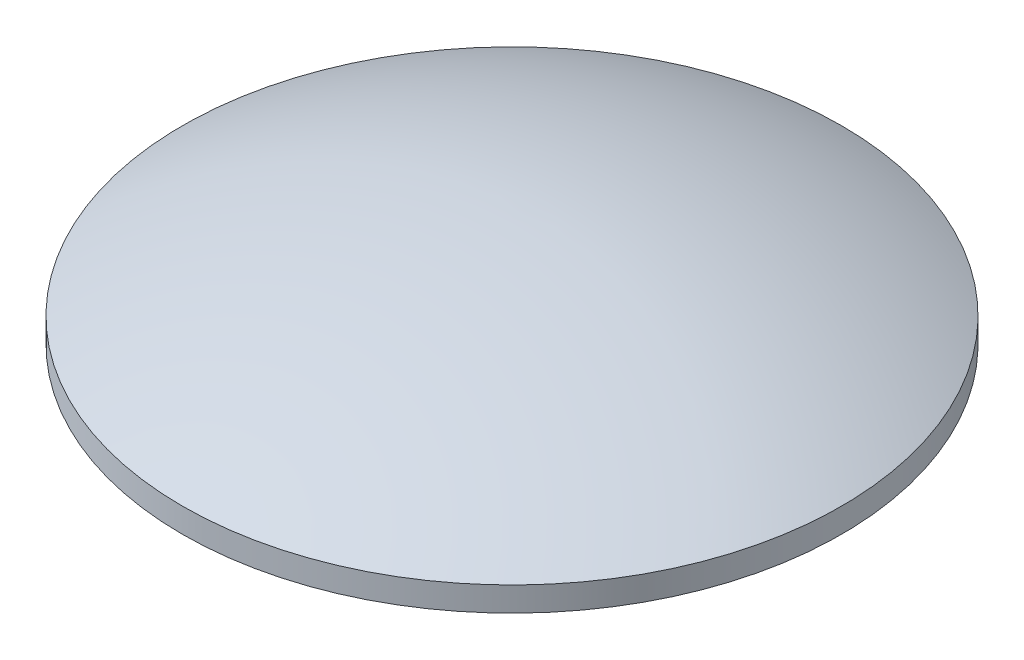
SolidWorks part; units mm, degrees
ref_plane "Front Plane" through (0, 0, 0) normal (0, 0, 1) x (1, 0, 0)
ref_plane "Top Plane" through (0, 0, 0) normal (0, 1, 0) x (1, 0, 0)
ref_plane "Right Plane" through (0, 0, 0) normal (1, 0, 0) x (0, 0, -1)
sketch "Sketch2" plane through (0, 0, 0) normal (0, 1, 0) x (1, 0, 0)
  circle A0 centre (0, 0) radius 6.75
  dimension "D1" = 13.5
extrude "Boss-Extrude1" add sketch "Sketch2" along normal blind 0.5
dome "Dome1" faces to dome 1 distance 1.7 reverse direction no elliptical dome no face at (0, 0.5, 6.75) parameters "D1"=1.7
sketch "Sketch3" plane through (0, 0, 0) normal (0, -1, 0) x (1, 0, 0)
  circle A0 centre (0, 0) radius 2.5631
